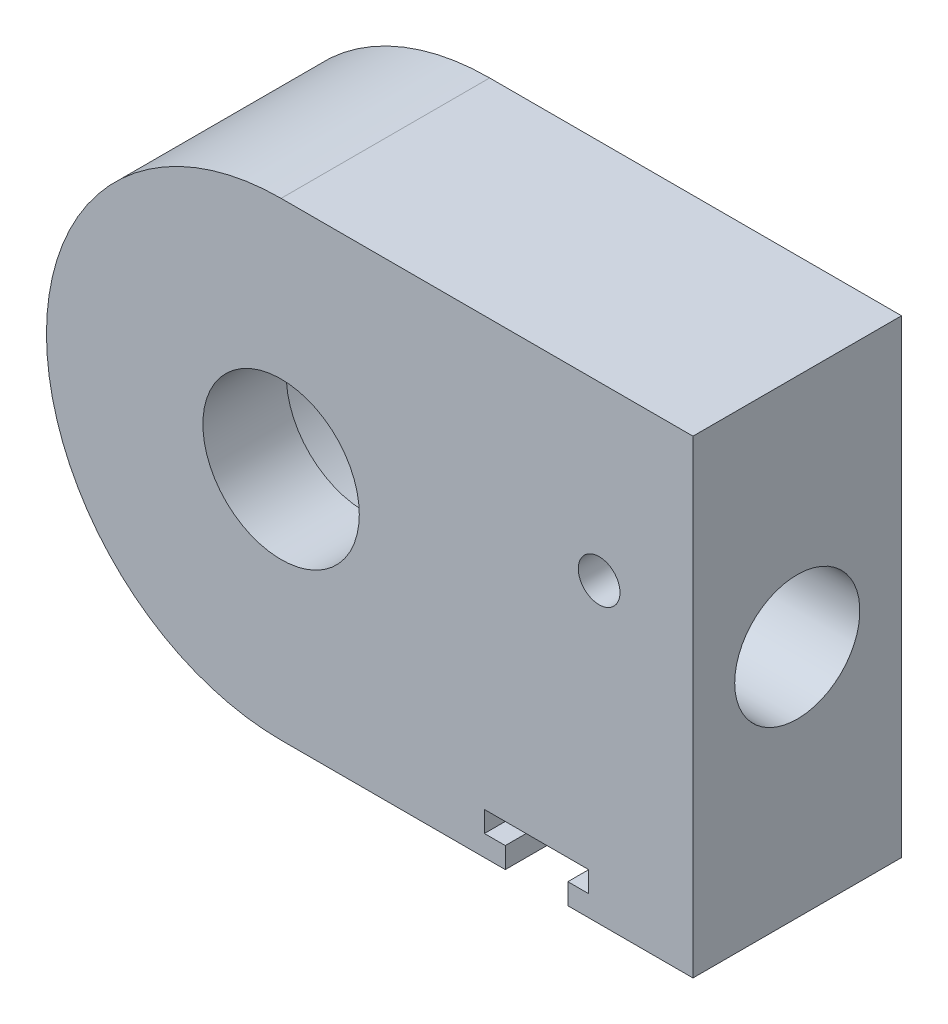
SolidWorks part; units mm, degrees
ref_plane "Plan de face" through (0, 0, 0) normal (0, 0, 1) x (1, 0, 0)
ref_plane "Plan de dessus" through (0, 0, 0) normal (0, 1, 0) x (1, 0, 0)
ref_plane "Plan de droite" through (0, 0, 0) normal (1, 0, 0) x (0, 0, -1)
sketch "Esquisse1" plane through (0, 0, 0) normal (0, 0, 1) x (1, 0, 0)
  line L0 (-634.5081, 20) -> (-595.0087, 20)
  line L1 (-595.0087, 20) -> (-595.0087, -25)
  line L2 (-595.0087, -25) -> (-634.5081, -25)
  line L3 (-666.113, -2.5) -> (-573.9627, -2.5) construction
  line L4 (-613.0087, -25) -> (-613.0087, -23)
  line L5 (-595.0087, -2.5) -> (-612.0087, -2.5)
  line L6 (-595.0087, -2.5) -> (-595.0087, 3.5)
  line L7 (-595.0087, 3.5) -> (-612.0087, 3.5)
  line L8 (-612.0087, -2.5) -> (-612.0087, 3.5)
  line L9 (-605.0087, -23) -> (-605.0087, -21)
  line L10 (-613.0087, -23) -> (-615.0087, -23)
  line L11 (-615.0087, -23) -> (-615.0087, -21)
  line L12 (-615.0087, -21) -> (-605.0087, -21)
  line L15 (-607.0087, -23) -> (-605.0087, -23)
  line L16 (-607.0087, -23) -> (-607.0087, -25)
  circle A0 centre (-634.5081, -2.5) radius 7.5
  arc A1 (-634.5081, 20) -> (-634.5081, -25) centre (-634.5081, -2.5) ccw
  circle A2 centre (-606.8206, 14.5) radius 4
  circle A5 centre (-634.5081, -2.5) radius 14
  circle A7 centre (-604.0087, 3.5) radius 2
  point P22 (-610.0087, -21)
  dimension "D1" = 6
  dimension "D3" = 6
  dimension "D4" = 2
  dimension "D5" = 28
  dimension "D6" = 15
  dimension "D8" = 10
  dimension "D9" = 8
  dimension "D11" = 4
  dimension "D12" = 8
  dimension "D13" = 15
  dimension "D2" = 17
  dimension "D7" = 45
  dimension "D10" = 39.4994
  dimension "D14" = 4
extrude "Boss.-Extru.1" add sketch "Esquisse1" along normal mid plane 20 contours L1 L2 A1 L0 | A0
revolve "Enlèvement de matière-Révolution1" cut sketch "Esquisse1<3>" angle 360 about L3
sketch "Esquisse1<3>" plane through (0, 0, 0) normal (0, 0, 1) x (1, 0, 0) same geometry as "Esquisse1"
extrude "Enlèv. mat.-Extru.1" cut sketch "Esquisse1<5>" against normal blind 10 and the other way blind 2 contours A5
sketch "Esquisse1<5>" plane through (0, 0, 0) normal (0, 0, 1) x (1, 0, 0) same geometry as "Esquisse1"
extrude "Enlèv. mat.-Extru.2" cut sketch "Esquisse1<6>" against normal through all both and the other way through all contours A7
sketch "Esquisse1<6>" plane through (0, 0, 0) normal (0, 0, 1) x (1, 0, 0) same geometry as "Esquisse1"
extrude "Enlèv. mat.-Extru.3" cut sketch "Esquisse1<8>" against normal through all both and the other way through all contours L16 L15 L9 L12 L11 L10 L4 L2 region at (-610.0087, -22.75, 0)
sketch "Esquisse1<8>" plane through (0, 0, 0) normal (0, 0, 1) x (1, 0, 0) same geometry as "Esquisse1"
